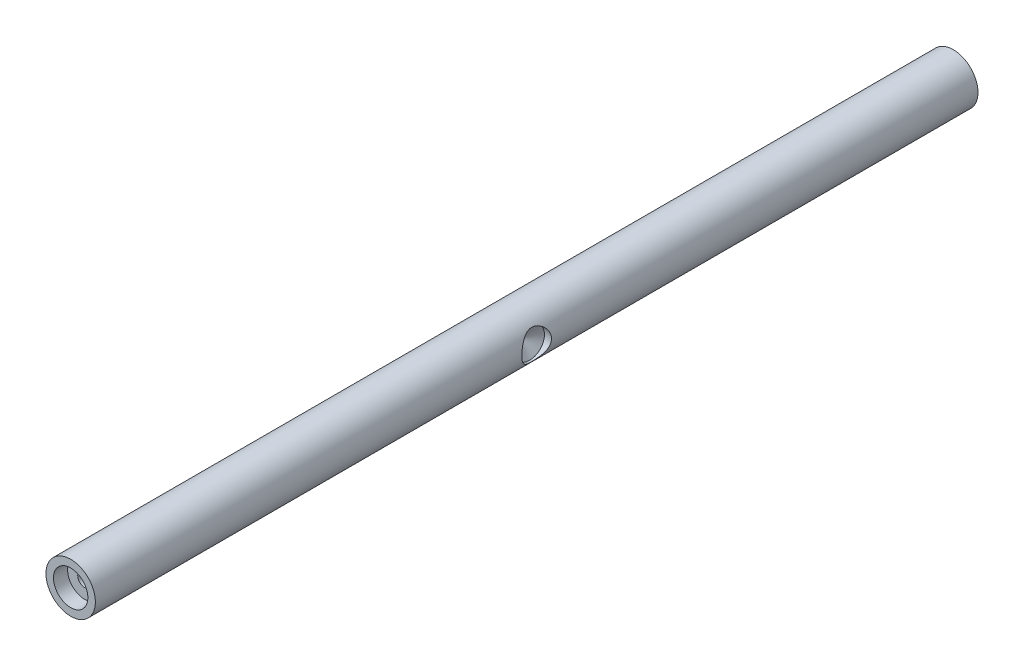
SolidWorks part; units mm, degrees
ref_plane "Piano frontale" through (0, 0, 0) normal (0, 0, 1) x (1, 0, 0)
ref_plane "Piano superiore" through (0, 0, 0) normal (0, 1, 0) x (1, 0, 0)
ref_plane "Piano destro" through (0, 0, 0) normal (1, 0, 0) x (0, 0, -1)
sketch "Schizzo1" plane through (0, 0, 0) normal (0, 0, 1) x (1, 0, 0)
  circle A0 centre (0, 0) radius 7
  dimension "D1" = 14
extrude "Estrusione-Estrusione1" add sketch "Schizzo1" along normal mid plane 250
sketch "Schizzo2" plane through (0, 0, 125) normal (0, 0, 1) x (1, 0, 0)
  circle A0 centre (0, 0) radius 2
  dimension "D1" = 4
extrude "Taglio-Estrusione1" cut sketch "Schizzo2" against normal up to next
sketch "Schizzo5" plane through (0, 0, 125) normal (0, 0, 1) x (1, 0, 0)
  circle A0 centre (0, 0) radius 4.87
extrude "Taglio-Estrusione2" cut sketch "Schizzo5" against normal blind 4
ref_plane "Piano1" through (7, 0, 0) normal (1, 0, 0) x (0, 0, -1)
hole_wizard "Foro per Vite M8-1" positions "Schizzo8" profile "Schizzo9" hole size "M8" standard "ISO"
sketch "Schizzo8" plane through (7, 0, 0) normal (1, 0, 0) x (0, 0, -1)
  point P0 (0, 0)
sketch "Schizzo9" plane through (7, 0, 0) normal (0, 1, 0) x (0, 0, -1)
  line L0 (0, 0) -> (0, 4.5236)
  line L1 (0, 4.5236) -> (4.2, 2)
  line L2 (4.2, 2) -> (4.2, 0)
  line L5 (4.2, 0) -> (0, 0)
  line L10 (0, 4.5236) -> (-4.2, 2) construction
  line L11 (0, -6.35) -> (0, 107.95) construction
  dimension "Hole Dia." = 8.4
  dimension "Hole Depth" = 2
  dimension "Drill Angle" = 118
